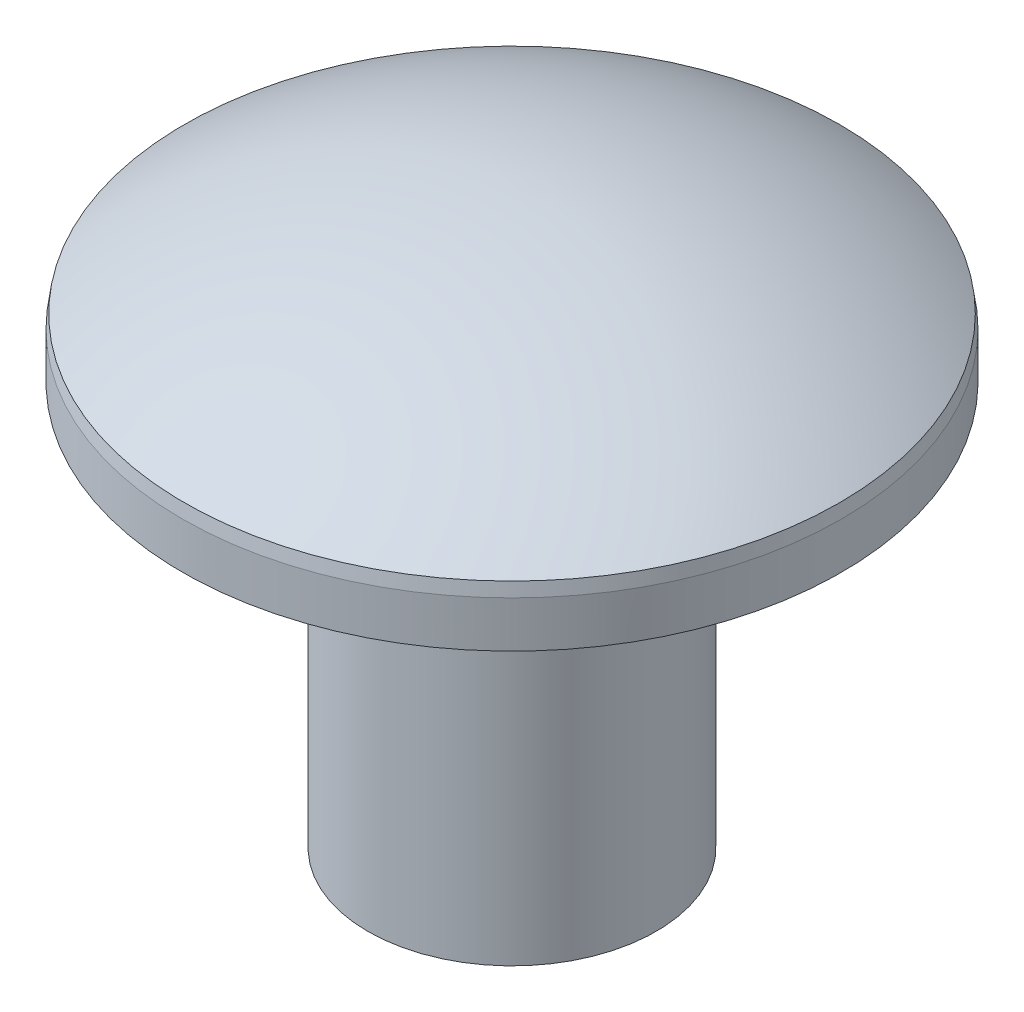
SolidWorks part; units mm, degrees
ref_plane "Front Plane" through (0, 0, 0) normal (0, 0, 1) x (1, 0, 0)
ref_plane "Top Plane" through (0, 0, 0) normal (0, 1, 0) x (1, 0, 0)
ref_plane "Right Plane" through (0, 0, 0) normal (1, 0, 0) x (0, 0, -1)
sketch "Sketch1" plane through (0, 0, 0) normal (0, 0, 1) x (1, 0, 0)
  line L0 (0, 0) -> (-30, 0)
  line L1 (0, 0) -> (0, 10)
  arc A0 (0, 10) -> (-30, 0) centre (0, -40) ccw
  dimension "D1" = 30
  dimension "D2" = 10
revolve "Revolve1" add sketch "Sketch1" angle 360 about L1
chamfer "Chamfer1" distance 2 angle 45 1 edges at (0, 0, -30) first distance on face at (0, 0, -30)
sketch "Sketch7" plane through (0, 0, 0) normal (0, -1, 0) x (1, 0, 0)
  circle A0 centre (0, 0) radius 28.5714
  circle A1 centre (0, 0) radius 28.5714 construction
extrude "Boss-Extrude2" add sketch "Sketch7" along normal blind 4
sketch "Sketch8" plane through (0, -4, 0) normal (0, -1, 0) x (1, 0, 0)
  circle A0 centre (0, 0) radius 12.5
  dimension "D1" = 25
extrude "Boss-Extrude3" add sketch "Sketch8" along normal blind 35
